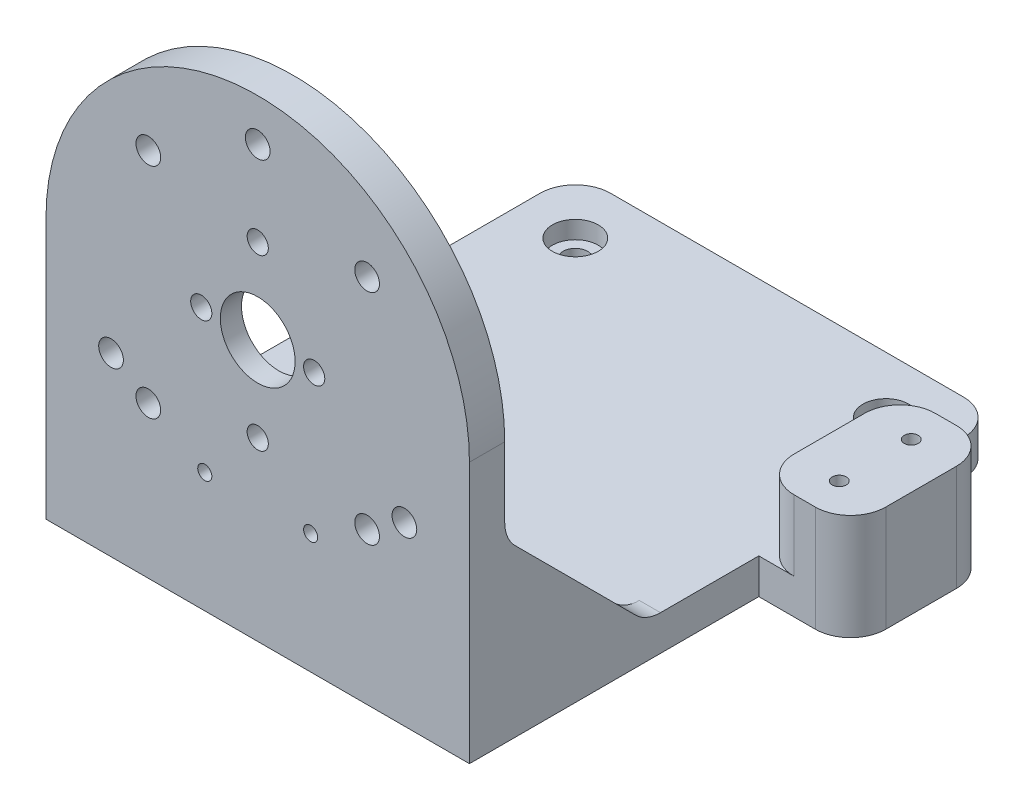
SolidWorks part; units mm, degrees
ref_plane "Plano frontal" through (0, 0, 0) normal (0, 0, 1) x (1, 0, 0)
ref_plane "Plano superior" through (0, 0, 0) normal (0, 1, 0) x (1, 0, 0)
ref_plane "Plano direito" through (0, 0, 0) normal (1, 0, 0) x (0, 0, -1)
sketch "Esboço1" plane through (0, 0, 0) normal (0, 0, 1) x (1, 0, 0)
  line L0 (-30, 0) -> (-30, -37)
  line L1 (-30, -37) -> (30, -37)
  line L2 (30, -37) -> (30, 0)
  circle A0 centre (0, 0) radius 5.3
  arc A1 (30, 0) -> (-30, 0) centre (0, 0) ccw
  dimension "D1" = 10.6
  dimension "D2" = 60
  dimension "D3" = 37
extrude "Ressalto-extrusão1" add sketch "Esboço1" along normal blind 5
sketch "Esboço2" plane through (0, 0, 0) normal (0, 0, -1) x (-1, 0, 0)
  line L0 (30, 0) -> (30, -37) construction
  line L1 (-30, -37) -> (30, -37)
  line L2 (-30, -37) -> (-30, -32)
  line L3 (-30, -32) -> (30, -32)
  line L4 (30, -37) -> (30, -32)
  dimension "D1" = 5
extrude "Ressalto-extrusão2" add sketch "Esboço2" along normal blind 70
sketch "Esboço5" plane through (0, 0, 0) normal (0, 0, -1) x (-1, 0, 0)
  circle A0 centre (0, 0) radius 16
  dimension "D1" = 32
extrude "Corte-extrusão2" cut sketch "Esboço5" against normal blind 2
fillet "Filete1" radius 5 2 edges at (-30, -34.5, -70) (30, -34.5, -70)
sketch "Esboço3" plane through (0, 0, 5) normal (0, 0, 1) x (1, 0, 0)
  circle A0 centre (0, 24) radius 1.75
  circle A1 centre (0, 0) radius 5.3 construction
  circle A2 centre (20.7846, -12) radius 1.75
  circle A3 centre (-20.7846, -12) radius 1.75
  point P11 (0, 0)
  dimension "D1" = 24
  dimension "D2" = 3.5
  dimension "D3" = 3
extrude "Corte-extrusão1" cut sketch "Esboço3" against normal through all
sketch "Esboço4" plane through (-30, 0, 0) normal (-1, 0, 0) x (0, 0, 1)
  line L0 (-20, -32) -> (0, -12)
  line L1 (-65, -32) -> (0, -32) construction
  line L2 (0, 0) -> (0, -32) construction
  line L3 (0, -12) -> (0, -32)
  line L4 (0, -32) -> (-20, -32)
  dimension "D1" = 20
  dimension "D2" = 20
extrude "Ressalto-extrusão3" add sketch "Esboço4" against normal blind 3
mirror "Espelhar1" about plane through (0, 0, 0) normal (1, 0, 0) of "Ressalto-extrusão3"
fillet "Filete2" radius 5 4 edges at (-28.5, -12, 0) (-28.5, -32, -20) (28.5, -32, -20) (28.5, -12, 0)
sketch "Esboço6" plane through (0, 0, 5) normal (0, 0, 1) x (1, 0, 0)
  line L0 (0, 5.3) -> (0, -5.3) construction
  circle A9 centre (-8, 0) radius 1.5
  circle A12 centre (0, 0) radius 5.3 construction
  circle A13 centre (8, 0) radius 1.5
  dimension "D1" = 8
  dimension "D2" = 3
extrude "Corte-extrusão3" cut sketch "Esboço6" against normal through all
sketch "Esboço8" plane through (0, 0, 5) normal (0, 0, 1) x (1, 0, 0)
  line L0 (-5.3, 0) -> (5.3, 0) construction
  circle A0 centre (0, 12) radius 1.5
  circle A1 centre (0, 0) radius 5.3 construction
  circle A2 centre (0, -12) radius 1.5
  dimension "D1" = 12
  dimension "D2" = 3
extrude "Corte-extrusão4" cut sketch "Esboço8" against normal through all
sketch "Esboço9" plane through (0, 0, 5) normal (0, 0, 1) x (1, 0, 0)
  circle A0 centre (-15.5, 15.5) radius 1.75
  circle A1 centre (15.5, 15.5) radius 1.75
  circle A2 centre (15.5, -15.5) radius 1.75
  circle A3 centre (-15.5, -15.5) radius 1.75
  point P12 (0, 0)
  dimension "D1" = 15.5
  dimension "D2" = 15.5
  dimension "D3" = 3.5
extrude "Corte-extrusão5" cut sketch "Esboço9" against normal through all
sketch "Esboço10" plane through (0, -32, 0) normal (0, 1, 0) x (1, 0, 0)
  line L0 (-25, 70) -> (25, 70) construction
  line L1 (-30, 65) -> (-30, 22.0711) construction
  line L2 (30, 65) -> (30, 22.0711) construction
  circle A0 centre (0, 8) radius 1.75
  circle A1 centre (-22, 62) radius 1.75
  circle A2 centre (22, 62) radius 1.75
  dimension "D1" = 3.5
  dimension "D2" = 3.5
  dimension "D3" = 3.5
  dimension "D4" = 8
  dimension "D5" = 8
  dimension "D6" = 8
  dimension "D7" = 8
  dimension "D8" = 8
extrude "Corte-extrusão6" cut sketch "Esboço10" against normal through all
sketch "Esboço11" plane through (0, -32, 0) normal (0, 1, 0) x (1, 0, 0)
  circle A0 centre (-22, 62) radius 3.25
  circle A1 centre (22, 62) radius 3.25
  circle A2 centre (0, 8) radius 3.25
  dimension "D1" = 6.5
  dimension "D2" = 6.5
  dimension "D3" = 6.5
extrude "Corte-extrusão7" cut sketch "Esboço11" against normal blind 2.5
sketch "Esboço13" plane through (0, -37, 0) normal (0, 1, 0) x (1, 0, 0)
  line L0 (30, 65) -> (30, 22.0711) construction
  line L1 (30, 56) -> (43, 56)
  line L2 (30, 56) -> (30, 36)
  line L3 (30, 36) -> (43, 36)
  line L4 (43, 56) -> (43, 36)
  line L5 (-25, 70) -> (25, 70) construction
  circle A0 centre (36.5, 51.1) radius 1
  circle A1 centre (36.5, 40.9) radius 1
  point P12 (36.5, 56)
  dimension "D4" = 10.2
  dimension "D5" = 4.9
  dimension "D6" = 2
  dimension "D7" = 2
  dimension "D8" = 0
  dimension "D9" = 0
  dimension "D1" = 13
  dimension "D2" = 20
  dimension "D3" = 14
extrude "Ressalto-extrusão4" add sketch "Esboço13" along normal blind 15
fillet "Filete3" radius 5 2 edges at (43, -29.5, -36) (43, -29.5, -56)
fillet "Filete4" radius 5 2 edges at (30, -27, -36) (30, -27, -56)
sketch "Esboço18" plane through (0, 0, 5) normal (0, 0, 1) x (1, 0, 0)
  circle A0 centre (-7.5, -20) radius 1
  circle A1 centre (7.5, -20) radius 1
  circle A2 centre (0, 0) radius 5.3 construction
  dimension "D1" = 7.5
  dimension "D2" = 7.5
  dimension "D3" = 0
  dimension "D4" = 20
  dimension "D5" = 2
  dimension "D6" = 2
extrude "Corte-extrusão9" cut sketch "Esboço18" against normal blind 4
